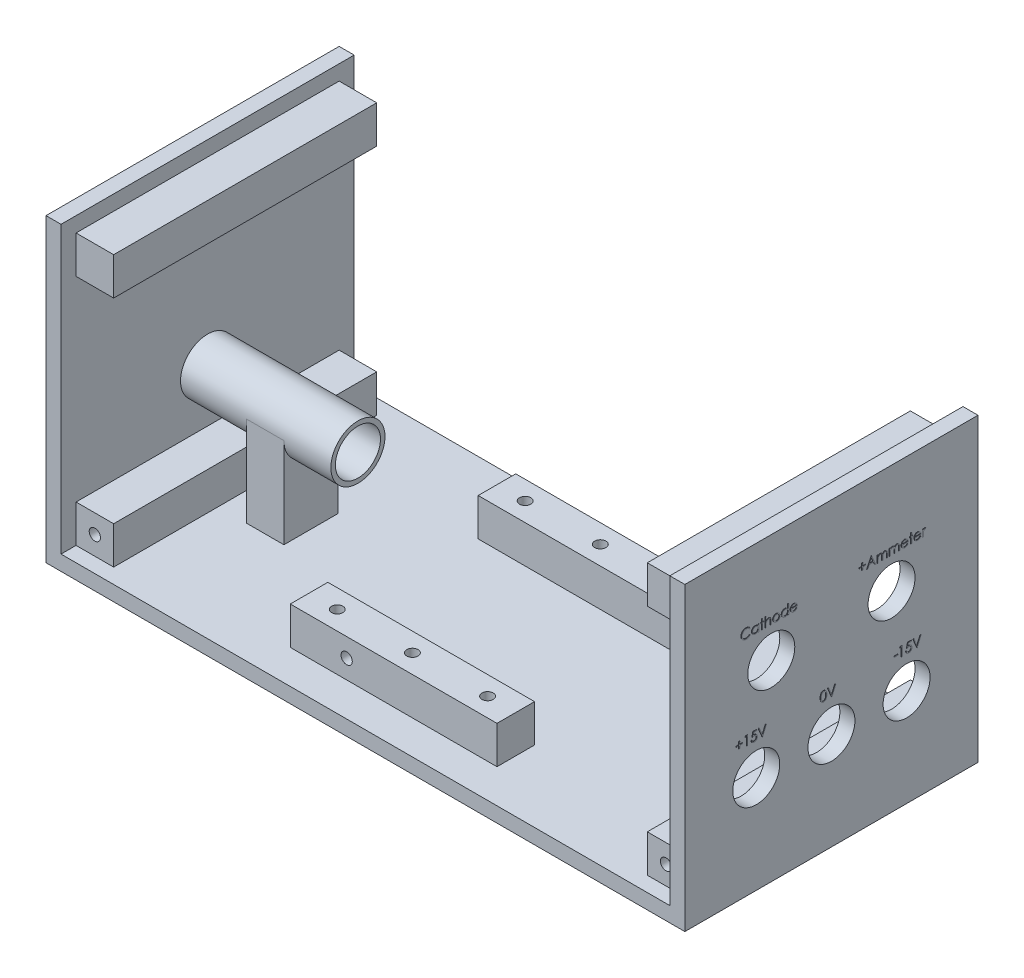
SolidWorks part; units mm, degrees
ref_plane "Front Plane" through (0, 0, 0) normal (0, 0, 1) x (1, 0, 0)
ref_plane "Top Plane" through (0, 0, 0) normal (0, 1, 0) x (1, 0, 0)
ref_plane "Right Plane" through (0, 0, 0) normal (1, 0, 0) x (0, 0, -1)
sketch "Sketch1" plane through (0, 0, 0) normal (0, 1, 0) x (1, 0, 0)
  line L1 (-85, -35) -> (85, -35)
  line L2 (-85, -35) -> (-85, 35)
  line L3 (-85, 35) -> (85, 35)
  line L4 (85, -35) -> (85, 35)
  line L5 (-85, -35) -> (85, 35) construction
  line L6 (-85, 35) -> (85, -35) construction
  point P0 (0, 0)
  dimension "D1" = 70
  dimension "D2" = 170
extrude "Base" add sketch "Sketch1" along normal blind 4
sketch "Sketch2" plane through (0, 4, 0) normal (0, 1, 0) x (1, 0, 0)
  line L0 (85, 35) -> (-85, 35) construction
  line L1 (-85, -35) -> (-81, -35)
  line L2 (-85, -35) -> (-85, 35)
  line L3 (-85, 35) -> (-81, 35)
  line L4 (-81, -35) -> (-81, 35)
  dimension "D1" = 4
extrude "In wall" add sketch "Sketch2" along normal blind 72
sketch "Sketch4" plane through (-85, 0, 0) normal (-1, 0, 0) x (0, 0, 1)
  line L0 (0, 28) -> (0, 0) construction
  circle A0 centre (0, 28) radius 6
  dimension "D1" = 12
  dimension "D2" = 28
extrude "Tube hole" cut sketch "Sketch4" against normal up to next
sketch "Sketch5" plane through (-81, 0, 0) normal (1, 0, 0) x (0, 0, -1)
  circle A0 centre (0, 28) radius 6 construction
  circle A1 centre (0, 28) radius 6
  circle A2 centre (0, 28) radius 7.2
  dimension "D1" = 1.2
extrude "Tube housing" add sketch "Sketch5" along normal blind 40
sketch "Sketch11" plane through (0, 4, 0) normal (0, 1, 0) x (1, 0, 0)
  line L0 (85, 35) -> (-81, 35) construction
  line L1 (81, -35) -> (71, -35)
  line L2 (81, -35) -> (81, 35)
  line L3 (81, 35) -> (71, 35)
  line L4 (71, -35) -> (71, 35)
  line L10 (85, 35) -> (-81, 35) construction
  line L15 (-81, -35) -> (-71, -35)
  line L16 (-81, -35) -> (-81, 35)
  line L17 (-81, 35) -> (-71, 35)
  line L18 (-71, -35) -> (-71, 35)
  line L19 (85, -35) -> (85, 35) construction
  line L20 (-81, -35) -> (85, -35) construction
  dimension "D1" = 10
  dimension "D2" = 4
extrude "Nut housing" add sketch "Sketch11" along normal blind 10
sketch "Sketch18" plane through (0, 4, 0) normal (0, 1, 0) x (1, 0, 0)
  line L0 (-29, 0) -> (-29, 20) construction
  line L1 (-29, 30) -> (26, 30)
  line L2 (-29, 30) -> (-29, 20)
  line L3 (-29, 20) -> (26, 20)
  line L4 (26, 30) -> (26, 20)
  line L5 (-29, -30) -> (26, -30)
  line L6 (-29, -30) -> (-29, -20)
  line L7 (-29, -20) -> (26, -20)
  line L8 (26, -30) -> (26, -20)
  line L17 (-29, 0) -> (26, 0) construction
  line L18 (26, -20) -> (26, 20) construction
  line L19 (-29, 0) -> (-41, 0) construction
  line L20 (-29, 0) -> (0, 0) construction
  line L21 (-41, -7.2) -> (-41, 7.2) construction
  line L22 (-1.5, 25) -> (26, 25) construction
  line L23 (-1.5, 20) -> (-1.5, 25) construction
  line L24 (-21.5, 25) -> (-1.5, 25) construction
  line L25 (-1.5, 25) -> (18.5, 25) construction
  line L26 (-21.5, -25) -> (-1.5, -25) construction
  line L28 (26, -25) -> (-1.5, -25) construction
  line L29 (-1.5, -25) -> (-1.5, -20) construction
  circle A0 centre (-1.5, 25) radius 1.5
  circle A3 centre (-1.5, -25) radius 1.5
  circle A4 centre (-21.5, 25) radius 1.5
  circle A5 centre (-21.5, -25) radius 1.5
  circle A6 centre (18.5, 25) radius 1.5
  circle A7 centre (18.5, -25) radius 1.5
  dimension "D1" = 10
  dimension "D2" = 3
  dimension "D3" = 50
  dimension "D4" = 12
  dimension "D5" = 55
  dimension "D6" = 20
  dimension "D7" = 20
extrude "PCB Stand" add sketch "Sketch18" along normal blind 10
sketch "Sketch12" plane through (0, 0, -35) normal (0, 0, -1) x (-1, 0, 0)
  line L0 (-76, 14) -> (-76, 9) construction
  line L1 (-81, 14) -> (-71, 14) construction
  line L2 (-76, 9) -> (-71, 9) construction
  line L3 (-71, 14) -> (-71, 4) construction
  line L4 (29, 14) -> (29, 4) construction
  line L8 (76, 9) -> (76, 14) construction
  line L9 (71, 14) -> (81, 14) construction
  line L10 (71, 9) -> (76, 9) construction
  line L11 (71, 14) -> (71, 4) construction
  circle A0 centre (-76, 9) radius 1.5
  circle A1 centre (14, 9) radius 1.5
  circle A2 centre (76, 9) radius 1.5
  point P13 (0, 0)
  dimension "D1" = 3
  dimension "D2" = 15
extrude "Nut L" cut sketch "Sketch12" against normal blind 10
sketch "Sketch13" plane through (0, 0, 35) normal (0, 0, 1) x (1, 0, 0)
  line L0 (-76, 9) -> (-71, 9) construction
  line L1 (-71, 14) -> (-71, 4) construction
  line L2 (-76, 14) -> (-76, 9) construction
  line L3 (-81, 14) -> (-71, 14) construction
  line L4 (-29, 14) -> (-29, 4) construction
  line L8 (71, 9) -> (76, 9) construction
  line L9 (71, 14) -> (71, 4) construction
  line L10 (76, 9) -> (76, 14) construction
  line L11 (71, 14) -> (81, 14) construction
  circle A0 centre (-76, 9) radius 1.5
  circle A1 centre (-14, 9) radius 1.5
  circle A2 centre (76, 9) radius 1.5
  dimension "D1" = 3
  dimension "D2" = 15
extrude "Nur R" cut sketch "Sketch13" against normal blind 10
sketch "Sketch15" plane through (0, 0, 0) normal (0, -1, 0) x (1, 0, 0)
  line L1 (-12.5, 12.5) -> (12.5, 12.5)
  line L2 (-12.5, 12.5) -> (-12.5, -12.5)
  line L3 (-12.5, -12.5) -> (12.5, -12.5)
  line L4 (12.5, 12.5) -> (12.5, -12.5)
  line L10 (-85, 0) -> (-12.5, 0) construction
  line L11 (-85, -35) -> (-85, 35) construction
  line L12 (0, 0) -> (12.5, 0) construction
  line L13 (0, 0) -> (0, 12.5) construction
  circle A0 centre (0, 0) radius 3
  dimension "D2" = 6
  dimension "D1" = 25
extrude "Nut for stand" add sketch "Sketch15" along normal blind 10
sketch "Sketch19" plane through (0, 4, 0) normal (0, 1, 0) x (1, 0, 0)
  line L1 (85, 35) -> (81, 35)
  line L2 (85, 35) -> (85, -35)
  line L3 (85, -35) -> (81, -35)
  line L4 (81, 35) -> (81, -35)
extrude "Back side wall" add sketch "Sketch19" along normal up to surface (72 mm away) up to face at (-83, 76, 0)
sketch "Sketch21" plane through (81, 0, 0) normal (-1, 0, 0) x (0, 0, 1)
  line L0 (35, 76) -> (35, 14) construction
  line L1 (-35, 76) -> (35, 76)
  line L2 (-35, 76) -> (-35, 66)
  line L3 (-35, 66) -> (35, 66)
  line L4 (35, 76) -> (35, 66)
  dimension "D1" = 10
extrude "Top nut housing" add sketch "Sketch21" along normal blind 10
sketch "Sketch22" plane through (-81, 0, 0) normal (1, 0, 0) x (0, 0, -1)
  line L0 (35, 76) -> (35, 14) construction
  line L1 (-35, 76) -> (35, 76)
  line L2 (-35, 76) -> (-35, 66)
  line L3 (-35, 66) -> (35, 66)
  line L4 (35, 76) -> (35, 66)
  dimension "D1" = 10
extrude "Top nut housing 2" add sketch "Sketch22" along normal blind 10
sketch "Sketch20" plane through (85, 0, 0) normal (1, 0, 0) x (0, 0, -1)
  line L1 (0, 51) -> (0, 26) construction
  line L2 (-20, 26) -> (0, 26) construction
  line L3 (20, 26) -> (0, 26) construction
  line L4 (-20, 26) -> (-20, 0) construction
  line L5 (-35, 0) -> (35, 0) construction
  line L6 (-35, 76) -> (-35, 0) construction
  line L8 (16, 51) -> (-16, 51) construction
  circle A0 centre (-20, 26) radius 6.25
  circle A1 centre (-16, 51) radius 6.25
  circle A3 centre (0, 26) radius 6.25
  circle A4 centre (20, 26) radius 6.25
  circle A5 centre (16, 51) radius 6.25
  dimension "D3" = 26
  dimension "D4" = 15
  dimension "D1" = 20
  dimension "D2" = 25
  dimension "D5" = 32
extrude "Banana jack holes" cut sketch "Sketch20" against normal up to next
sketch "Sketch23" plane through (85, 0, 0) normal (1, 0, 0) x (0, 0, -1)
  text T0 "+15V" font "Century Gothic" height 2.5
  text T1 "0V" font "Century Gothic" height 2.5
  text T2 "-15V" font "Century Gothic" height 2.5
  text T3 "+Ammeter" font "Century Gothic" height 2.5
  text T4 "Cathode" font "Century Gothic" height 2.5
extrude "Labels" add sketch "Sketch23" along normal blind 0.1
sketch "Sketch24" plane through (0, 4, 0) normal (0, 1, 0) x (1, 0, 0)
  line L0 (-81, -7.2) -> (-41, -7.2) construction
  line L1 (-53.494, 7.2) -> (-63.494, 7.2)
  line L2 (-53.494, 7.2) -> (-53.494, -7.2)
  line L3 (-53.494, -7.2) -> (-63.494, -7.2)
  line L4 (-63.494, 7.2) -> (-63.494, -7.2)
  dimension "D1" = 10
extrude "Boss-Extrude1" add sketch "Sketch24" along normal up to next
sketch "Sketch25" plane through (0, 76, 0) normal (0, 1, 0) x (1, 0, 0)
  line L0 (-85, -35) -> (-71, -35) construction
  line L1 (-85, 35) -> (-81, 35)
  line L2 (-85, 35) -> (-85, -35)
  line L3 (-85, -35) -> (-81, -35)
  line L4 (-81, 35) -> (-81, -35)
  line L5 (85, -35) -> (71, -35) construction
  line L6 (85, 35) -> (81, 35)
  line L7 (85, 35) -> (85, -35)
  line L8 (85, -35) -> (81, -35)
  line L9 (81, 35) -> (81, -35)
  dimension "D1" = 4
extrude "Fin1" add sketch "Sketch25" along normal blind 4
sketch "Sketch26" plane through (0, 0, 35) normal (0, 0, 1) x (1, 0, 0)
  line L1 (-81, 80) -> (-85, 80)
  line L2 (-81, 80) -> (-81, 0)
  line L3 (-81, 0) -> (-85, 0)
  line L4 (-85, 80) -> (-85, 0)
extrude "Fin2" add sketch "Sketch26" along normal blind 4
sketch "Sketch27" plane through (0, 0, 35) normal (0, 0, 1) x (1, 0, 0)
  line L1 (81, 80) -> (85, 80)
  line L2 (81, 80) -> (81, 0)
  line L3 (81, 0) -> (85, 0)
  line L4 (85, 80) -> (85, 0)
extrude "Boss-Extrude4" add sketch "Sketch27" along normal blind 4
sketch "Sketch28" plane through (0, 0, -35) normal (0, 0, -1) x (-1, 0, 0)
  line L1 (81, 80) -> (85, 80)
  line L2 (81, 80) -> (81, 0)
  line L3 (81, 0) -> (85, 0)
  line L4 (85, 80) -> (85, 0)
  line L5 (-81, 80) -> (-85, 80)
  line L6 (-81, 80) -> (-81, 0)
  line L7 (-81, 0) -> (-85, 0)
  line L8 (-85, 80) -> (-85, 0)
extrude "Boss-Extrude5" add sketch "Sketch28" along normal blind 4
sketch "Sketch29" plane through (0, 0, 35) normal (0, 0, 1) x (1, 0, 0)
  line L0 (-81, 0) -> (-81, 14) construction
  line L1 (81, 0) -> (-81, 0)
  line L2 (81, 0) -> (81, 4)
  line L3 (81, 4) -> (-81, 4)
  line L4 (-81, 0) -> (-81, 4)
  line L5 (-71, 4) -> (71, 4) construction
extrude "Boss-Extrude6" add sketch "Sketch29" along normal blind 4
sketch "Sketch30" plane through (0, 0, -35) normal (0, 0, -1) x (-1, 0, 0)
  line L1 (-81, 0) -> (81, 0)
  line L2 (-81, 0) -> (-81, 4)
  line L3 (-81, 4) -> (81, 4)
  line L4 (81, 0) -> (81, 4)
  line L5 (-71, 4) -> (71, 4) construction
  line L6 (81, 14) -> (81, 0) construction
extrude "Boss-Extrude7" add sketch "Sketch30" along normal blind 4
sketch "Sketch31" plane through (-85, 0, 0) normal (-1, 0, 0) x (0, 0, 1)
  line L0 (0, 28) -> (12, 28) construction
  line L5 (0, 28) -> (-12, 28) construction
  line L6 (0, 28) -> (0, 16) construction
  line L7 (0, 28) -> (0, 40) construction
  line L9 (-0.4722, 45) -> (0.4722, 45)
  line L10 (-0.4722, 45) -> (-0.4722, 35)
  line L11 (-0.4722, 35) -> (0.4722, 35)
  line L12 (0.4722, 45) -> (0.4722, 35)
  line L13 (-0.4722, 45) -> (0.4722, 35) construction
  line L14 (-0.4722, 35) -> (0.4722, 45) construction
  line L15 (-7, 28.4722) -> (-17, 28.4722)
  line L16 (-7, 28.4722) -> (-7, 27.5278)
  line L17 (-7, 27.5278) -> (-17, 27.5278)
  line L18 (-17, 28.4722) -> (-17, 27.5278)
  line L19 (-7, 28.4722) -> (-17, 27.5278) construction
  line L20 (-7, 27.5278) -> (-17, 28.4722) construction
  line L21 (-0.4722, 11) -> (0.4722, 11)
  line L22 (-0.4722, 11) -> (-0.4722, 21)
  line L23 (-0.4722, 21) -> (0.4722, 21)
  line L24 (0.4722, 11) -> (0.4722, 21)
  line L25 (-0.4722, 11) -> (0.4722, 21) construction
  line L26 (-0.4722, 21) -> (0.4722, 11) construction
  line L27 (7, 28.4722) -> (17, 28.4722)
  line L28 (7, 28.4722) -> (7, 27.5278)
  line L29 (7, 27.5278) -> (17, 27.5278)
  line L30 (17, 28.4722) -> (17, 27.5278)
  line L31 (7, 28.4722) -> (17, 27.5278) construction
  line L32 (7, 27.5278) -> (17, 28.4722) construction
  text T0 " APERTURE"
  dimension "D1" = 10
  dimension "D2" = 12
extrude "Label aperture" add sketch "Sketch31" along normal blind 0.1
equation "\"t1\"=4"
equation "\"D1@Sketch2\"=\"t1\""
equation "\"H\"= 72"
equation "\"D1@In wall\" = \"H\""
equation "\"base_w\"= 70"
equation "\"D1@Sketch1\"=\"base_w\""
equation "\"base_L\"= 170"
equation "\"D2@Sketch1\"=\"base_L\""
equation "\"tube_hole_d\"= 12"
equation "\"D1@Sketch4\"=\"tube_hole_d\""
equation "\"nut_housing\"=10"
equation "\"D1@Sketch11\"=\"nut_housing\""
equation "\"D1@Nut housing\" = \"nut_housing\""
equation "\"D1@Sketch18\"=\"nut_housing\""
equation "\"pcb_stand_height\"= 10"
equation "\"D1@PCB Stand\"=\"pcb_stand_height\""
equation "\"slot_dist\"=50"
equation "\"D3@Sketch18\"=\"slot_dist\""
equation "\"D2@Sketch11\"=\"t1\""
equation "\"tube_hole_bottom\"=28"
equation "\"D2@Sketch4\"=\"tube_hole_bottom\""
equation "\"jack_hole_d\"=12.5"
equation "\"D1@Sketch21\"=\"nut_housing\""
equation "\"D1@Top nut housing\"=\"nut_housing\""
equation "\"D1@Sketch22\"=\"nut_housing\""
equation "\"D1@Top nut housing 2\" = \"nut_housing\""
equation "\"banana_hole_dist\"= 25"
equation "\"banana_hole_bottom\"= 26"
equation "\"D3@Sketch20\"=\"banana_hole_bottom\""
equation "\"banana_hole_left\"=15"
equation "\"D4@Sketch20\"=\"banana_hole_left\""
equation "\"banana_hole_dist2\"=20"
equation "\"D1@Sketch20\"=\"banana_hole_dist2\""
equation "\"D2@Sketch20\"=\"banana_hole_dist\""
equation "\"t2\"=2"
equation "\"D1@Sketch25\"=\"t1\""
equation "\"D1@Fin2\" = \"t1\""
